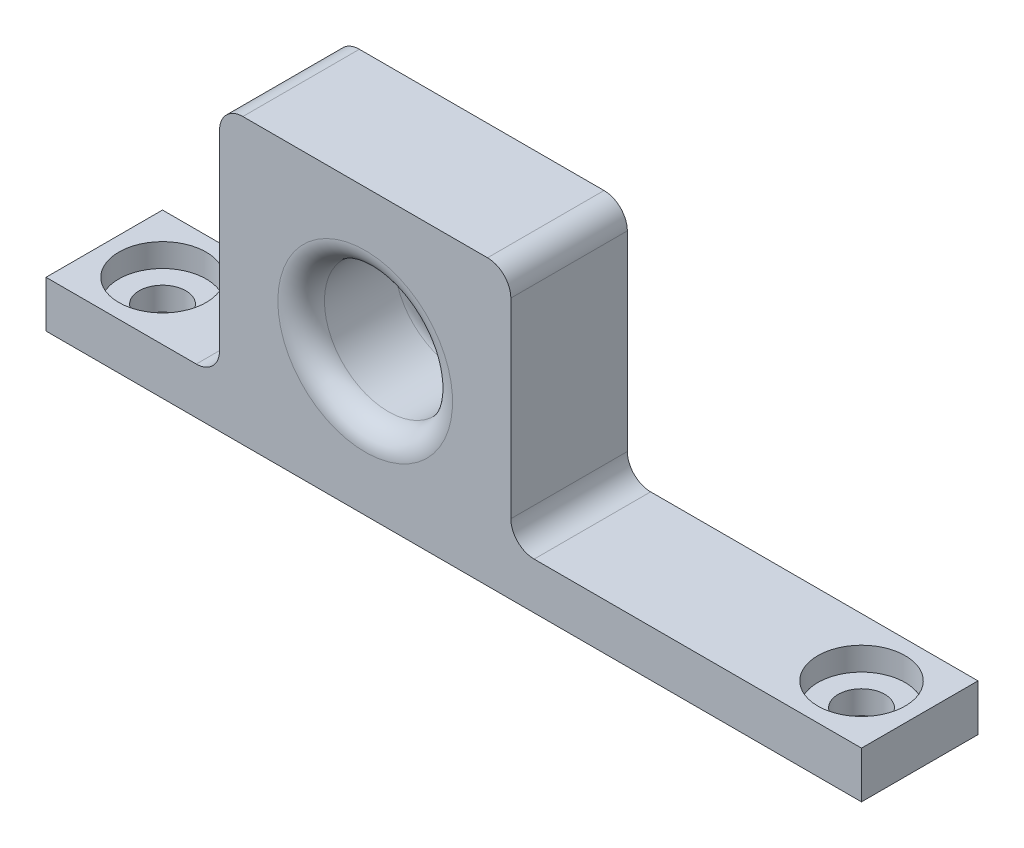
SolidWorks part; units mm, degrees
ref_plane "Front Plane" through (0, 0, 0) normal (0, 0, 1) x (1, 0, 0)
ref_plane "Top Plane" through (0, 0, 0) normal (0, 1, 0) x (1, 0, 0)
ref_plane "Right Plane" through (0, 0, 0) normal (1, 0, 0) x (0, 0, -1)
sketch "Sketch1" plane through (0, 0, 0) normal (0, 1, 0) x (1, 0, 0)
  line L0 (0, 6.35) -> (88.9, 6.35) construction
  line L1 (0, 0) -> (88.9, 0)
  line L2 (0, 0) -> (0, 12.7)
  line L3 (0, 12.7) -> (88.9, 12.7)
  line L4 (88.9, 0) -> (88.9, 12.7)
  line L5 (44.45, 12.7) -> (44.45, 0) construction
  circle A0 centre (6.35, 6.35) radius 2.54
  circle A1 centre (82.55, 6.35) radius 2.54
  dimension "D5" = 5.08
  dimension "D6" = 5.08
  dimension "D1" = 12.7
  dimension "D2" = 88.9
  dimension "D3" = 76.2
  dimension "D4" = 38.1
extrude "Boss-Extrude2" add sketch "Sketch1" along normal blind 5.08
sketch "Sketch3" plane through (0, 5.08, 0) normal (0, 1, 0) x (1, 0, 0)
  circle A0 centre (6.35, 6.35) radius 4.7625
  circle A1 centre (82.55, 6.35) radius 4.7625
  dimension "D1" = 9.525
  dimension "D2" = 9.525
extrude "Cut-Extrude1" cut sketch "Sketch3" against normal blind 2.54
sketch "Sketch4" plane through (0, 0, 0) normal (0, 0, 1) x (1, 0, 0)
  line L0 (0, 0) -> (88.9, 0) construction
  line L1 (18.923, 30.988) -> (50.673, 30.988)
  line L2 (18.923, 30.988) -> (18.923, 0)
  line L3 (18.923, 0) -> (50.673, 0)
  line L4 (50.673, 30.988) -> (50.673, 0)
  line L5 (88.9, 5.08) -> (88.9, 0) construction
  line L7 (34.798, 30.988) -> (34.798, 15.494) construction
  circle A0 centre (34.798, 15.494) radius 6.985
  point P12 (0, 0)
  point P15 (0, 0)
  dimension "D2" = 13.97
  dimension "D1" = 30.988
  dimension "D3" = 15.494
  dimension "D4" = 31.75
  dimension "D5" = 54.102
extrude "Boss-Extrude3" add sketch "Sketch4" against normal blind 12.7
fillet "Fillet1" radius 2.54 6 edges at (41.783, 15.494, 0) (41.783, 15.494, -12.7) (50.673, 5.08, -6.35) (50.673, 30.988, -6.35) (18.923, 30.988, -6.35) (18.923, 5.08, -6.35)
